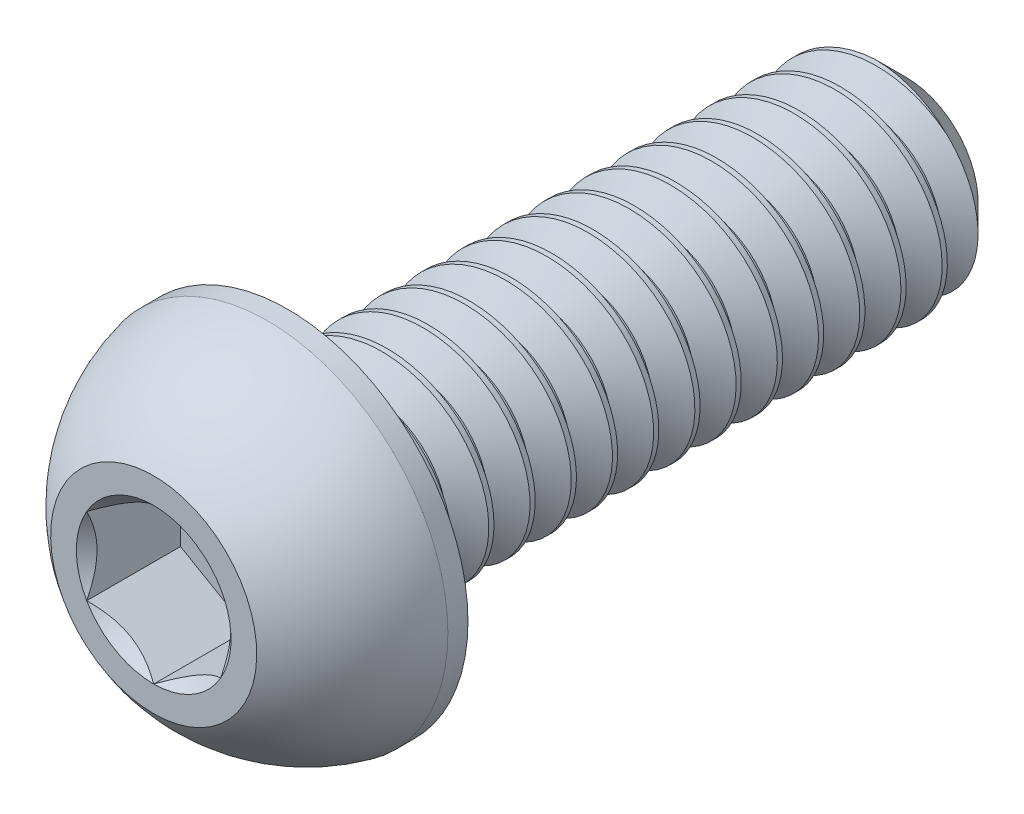
SolidWorks part; units mm, degrees
note: '?' marks a value the reader was unsure of.
ref_plane "Front" through (0, 0, 0) normal (0, 0, 1) x (1, 0, 0)
ref_plane "Top" through (0, 0, 0) normal (0, 1, 0) x (1, 0, 0)
ref_plane "Right" through (0, 0, 0) normal (1, 0, 0) x (0, 0, -1)
sketch "Sketch1" plane through (0, 0, 0) normal (1, 0, 0) x (0, 0, -1)
  line L2 (1.3, 1) -> (7.3, 1)
  line L3 (7.3, 1) -> (7.3, 0)
  line L4 (7.3, 0) -> (1.3, 0)
  line L6 (1.105, 1.75) -> (1.3, 1.75) construction
  line L7 (7.3, 1) -> (7.3, -1) construction
  line L8 (0, 0) -> (1.3, 0) construction
  line L9 (1.3, 1.75) -> (1.3, -1.75) construction
  line L11 (1.3, 1) -> (1.3, 0)
  line L13 (0, 0.65) -> (0, -0.65) construction
  line L14 (0, 0.65) -> (0, 1) construction
  arc A3 (0, 1) -> (1.105, 1.75) centre (1.4858, 0) cw construction
  dimension "D1" = 0.195
  dimension "Head Ht" = 1.3
  dimension "Head Dia" = 3.5
  dimension "Dia" = 2
  dimension "Lg" = 6
  dimension "Hex" = 1.3
revolve "Revolve1" add sketch "Sketch1" angle 360 mid plane about L4
sketch "Sketch3" plane through (0, 0, -7.3) normal (0, 0, -1) x (-1, 0, 0)
  circle A0 centre (0, 0) radius 1
curve "Helix/Spiral1" pitch 0.4 height 6.4 turns 16
chamfer "Chamfer1" distance 0.3 angle 45 1 edges at (0, 1, -7.3)
sketch "Sketch7" plane through (0, 0, 0) normal (1, 0, 0) x (0, 0, -1)
  line L6 (1.105, 1.75) -> (1.3, 1.75) construction
  line L8 (0, 0) -> (1.3, 0) construction
  line L11 (1.3, 1.75) -> (1.3, -1.75) construction
  line L12 (1.105, 1.75) -> (1.3, 1.75)
  line L13 (0, 0) -> (1.3, 0)
  line L14 (0, 0.65) -> (0, -0.65) construction
  line L15 (1.3, 1.75) -> (1.3, 0)
  line L16 (0, 1) -> (0, 0)
  arc A2 (1.105, 1.75) -> (0, 1) centre (1.4858, 0) ccw construction
  arc A3 (1.105, 1.75) -> (0, 1) centre (1.4858, 0) ccw
revolve "Revolve2" add sketch "Sketch7" angle 360 mid plane about L13
sketch "Sketch5" plane through (0, 0, 0) normal (0, 0, 1) x (1, 0, 0)
  line L1 (0.65, -0.3753) -> (0.65, 0.3753)
  line L2 (0.65, 0.3753) -> (0, 0.7506)
  line L3 (0, 0.7506) -> (-0.65, 0.3753)
  line L4 (-0.65, 0.3753) -> (-0.65, -0.3753)
  line L5 (-0.65, -0.3753) -> (0, -0.7506)
  line L6 (0, -0.7506) -> (0.65, -0.3753)
  circle A0 centre (0, 0) radius 0.65 construction
extrude "Cut-Extrude2" cut sketch "Sketch5" against normal blind 0.91
sketch "Sketch6" plane through (0, 0, 0) normal (0, 0, 1) x (1, 0, 0)
  circle A0 centre (0, 0) radius 0.7506
extrude "Cut-Extrude3" cut sketch "Sketch6" against normal blind 0.91 draft 45
sketch "Sketch2" plane through (0, 0, 0) normal (1, 0, 0) x (0, 0, -1)
  line L0 (7, 1) -> (7.35, 1)
  line L1 (7.35, 1) -> (7.2, 0.7402)
  line L2 (7.2, 0.7402) -> (7.15, 0.7402)
  line L3 (7.15, 0.7402) -> (7, 1)
  line L4 (7.075, 0.8701) -> (7.275, 0.8701) construction
  dimension "D1" = 60
  dimension "D2" = 0.05
  dimension "D3" = 0.2
sweep "Cut-Sweep1" cut profiles "Sketch2" path "Helix/Spiral1"
sketch "Sketch10" plane through (0, 0, 0) normal (1, 0, 0) x (0, 0, -1)
  line L0 (7.3, 1) -> (7.3, -1) construction
  point P0 (6.7, -1)
  dimension "D1" = 0.6
ref_axis "Center Axis 1" through (0, 0, -8.1113) along (0, 0, 1)?
ref_plane "Contact Plane 1" through (0, 0, -1.3) normal (0, 0, -1) x (-1, 0, 0)
ref_plane "Contact Plane 2" through (0, 0, 0) normal (0, 0, 1) x (1, 0, 0)
equation "\"D3@Helix/Spiral1\" = \"Lg@Sketch1\" + \"D4@Helix/Spiral1\""
equation "\"D2@Sketch2\" = \"D4@Helix/Spiral1\" * .125"
equation "\"D3@Sketch2\" = \"D4@Helix/Spiral1\" * .5"
equation "\"D1@Chamfer1\" = \"D4@Helix/Spiral1\" * .75"
equation "\"D1@Cut-Extrude2\" = \"Head Ht@Sketch1\" * .7"
equation "\"D1@Sketch1\" = \"Head Ht@Sketch1\" * .15"
equation "\"D1@Sketch10\" = \"D4@Helix/Spiral1\" * 1.5"
equation "\"D1@Cut-Extrude3\" = \"D1@Cut-Extrude2\""
